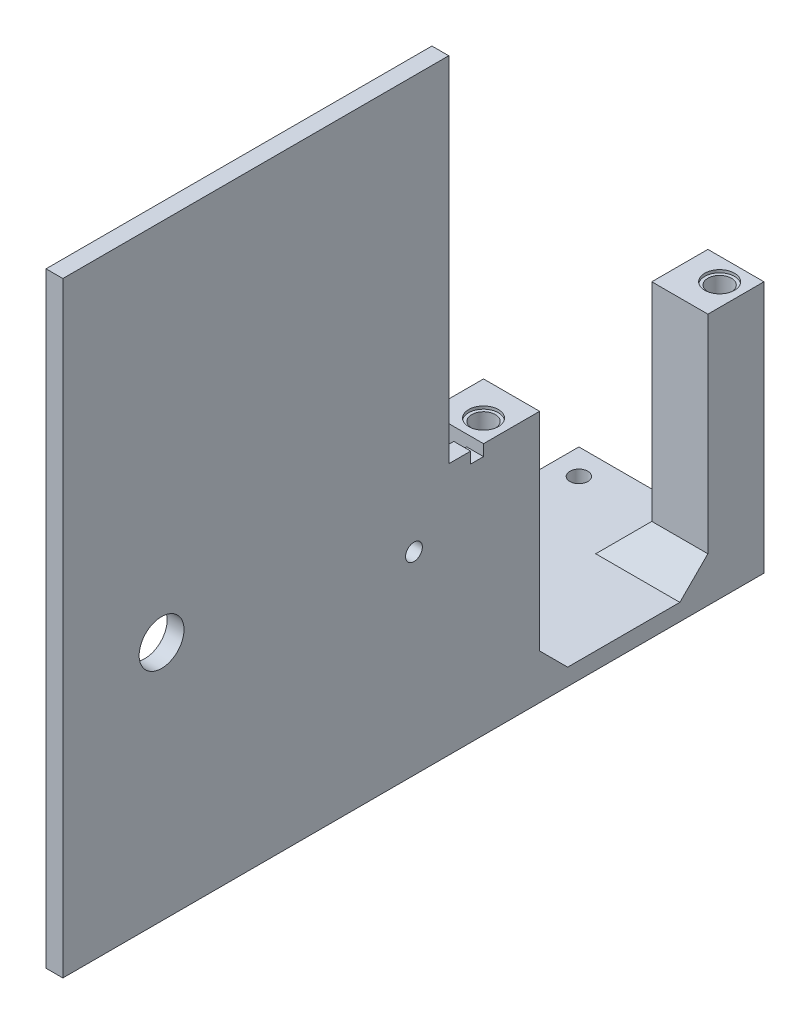
SolidWorks part; units mm, degrees
ref_plane "Front Plane" through (0, 0, 0) normal (0, 0, 1) x (1, 0, 0)
ref_plane "Top Plane" through (0, 0, 0) normal (0, 1, 0) x (1, 0, 0)
ref_plane "Right Plane" through (0, 0, 0) normal (1, 0, 0) x (0, 0, -1)
sketch "Sketch1" plane through (0, 0, 0) normal (0, 1, 0) x (1, 0, 0)
  line L1 (-6.5124, 9.686) -> (1.4876, 9.686)
  line L2 (-6.5124, 9.686) -> (-6.5124, -40.314)
  line L3 (-6.5124, -40.314) -> (1.4876, -40.314)
  line L4 (1.4876, 9.686) -> (1.4876, -40.314)
  line L5 (1.4876, 9.686) -> (26.4876, 9.686)
  line L6 (1.4876, 9.686) -> (1.4876, -40.314)
  line L7 (1.4876, -40.314) -> (26.4876, -40.314)
  line L8 (26.4876, 9.686) -> (26.4876, -40.314)
  circle A0 centre (-1.9624, -35.764) radius 1.6
  circle A1 centre (-1.9624, 5.136) radius 1.6
  dimension "D4" = 3.2
  dimension "D5" = 3.2
  dimension "D6" = 4.55
  dimension "D7" = 4.55
  dimension "D8" = 4.55
  dimension "D9" = 4.55
  dimension "D1" = 8
  dimension "D2" = 50
  dimension "D3" = 25
extrude "Boss-Extrude1" add sketch "Sketch1" along normal blind 3 contours A1 | A0 | L5 L8 L7 L3 L2 L1
sketch "Sketch2" plane through (0, 3, 0) normal (0, 1, 0) x (1, 0, 0)
  line L1 (26.4876, -40.314) -> (16.4876, -40.314)
  line L2 (26.4876, -40.314) -> (26.4876, -30.314)
  line L3 (26.4876, -30.314) -> (16.4876, -30.314)
  line L4 (16.4876, -40.314) -> (16.4876, -30.314)
  line L5 (26.4876, 9.686) -> (16.4876, 9.686)
  line L6 (26.4876, 9.686) -> (26.4876, -0.314)
  line L7 (26.4876, -0.314) -> (16.4876, -0.314)
  line L8 (16.4876, 9.686) -> (16.4876, -0.314)
  dimension "D1" = 10
  dimension "D2" = 10
  dimension "D3" = 10
  dimension "D4" = 10
extrude "Boss-Extrude2" add sketch "Sketch2" along normal blind 42
chamfer "Chamfer1" distance 5 angle 45 4 edges at (16.4876, 3, -4.686) (21.4876, 3, 0.314) (16.4876, 3, 35.314) (21.4876, 3, 30.314)
ref_plane "Plane1" through (0, 45, 0) normal (0, 1, 0) x (1, 0, 0)
sketch "Sketch3" plane through (0, 45, 0) normal (0, 1, 0) x (1, 0, 0)
  line L0 (26.4876, -40.314) -> (26.4876, -30.314) construction
  line L1 (16.4876, -40.314) -> (26.4876, -40.314) construction
  line L2 (26.4876, -0.314) -> (26.4876, 9.686) construction
  line L3 (26.4876, 9.686) -> (16.4876, 9.686) construction
  circle A0 centre (22.5376, -36.364) radius 2.1
  circle A1 centre (22.5376, 5.736) radius 2.1
  dimension "D1" = 4.2
  dimension "D3" = 3.95
  dimension "D4" = 4.2
  dimension "D6" = 3.95
  dimension "D2" = 3.95
  dimension "D5" = 3.95
extrude "Cut-Extrude1" cut sketch "Sketch3" against normal blind 52
sketch "Sketch4" plane through (0, 45, 0) normal (0, 1, 0) x (1, 0, 0)
  circle A0 centre (22.5376, -36.364) radius 2.65
  circle A1 centre (22.5376, 5.736) radius 2.65
  dimension "D1" = 5.3
  dimension "D2" = 5.3
extrude "Cut-Extrude2" cut sketch "Sketch4" against normal blind 0.5
ref_plane "Plane2" through (0, 22.5, 0) normal (0, -1, 0) x (-1, 0, 0)
mirror "Mirror1" about plane through (0, 22.5, 0) normal (0, -1, 0) of "Cut-Extrude2"
sketch "Sketch5" plane through (0, 0, 40.314) normal (0, 0, 1) x (1, 0, 0)
  line L0 (26.4876, 45) -> (26.4876, 0) construction
  line L1 (26.4876, 43) -> (23.4876, 43)
  line L2 (26.4876, 43) -> (26.4876, 0)
  line L3 (26.4876, 0) -> (23.4876, 0)
  line L4 (23.4876, 43) -> (23.4876, 0)
  line L5 (-6.5124, 0) -> (26.4876, 0) construction
  line L6 (16.4876, 45) -> (26.4876, 45) construction
  dimension "D1" = 3
  dimension "D2" = 2
extrude "Boss-Extrude3" add sketch "Sketch5" along normal blind 75
sketch "Sketch6" plane through (0, 43, 0) normal (0, 1, 0) x (1, 0, 0)
  line L0 (23.4876, -115.314) -> (23.4876, -40.314) construction
  line L1 (23.4876, -42.614) -> (26.4876, -42.614)
  line L2 (23.4876, -42.614) -> (23.4876, -46.514)
  line L3 (23.4876, -46.514) -> (26.4876, -46.514)
  line L4 (26.4876, -42.614) -> (26.4876, -46.514)
  line L5 (26.4876, -115.314) -> (26.4876, -40.314) construction
  line L6 (16.4876, -40.314) -> (26.4876, -40.314) construction
  dimension "D1" = 2.3
  dimension "D2" = 3.9
extrude "Boss-Extrude4" add sketch "Sketch6" along normal up to surface (2 mm away) up to face at (22.5376, 45, 39.014)
sketch "Sketch7" plane through (0, 43, 0) normal (0, 1, 0) x (1, 0, 0)
  line L1 (23.4876, -115.314) -> (26.4876, -115.314)
  line L2 (23.4876, -115.314) -> (23.4876, -46.514)
  line L3 (23.4876, -46.514) -> (26.4876, -46.514)
  line L4 (26.4876, -115.314) -> (26.4876, -46.514)
extrude "Boss-Extrude5" add sketch "Sketch7" along normal blind 5
sketch "Sketch8" plane through (23.4876, 0, 0) normal (-1, 0, 0) x (0, 0, 1)
  circle A0 centre (52.714, 34.5) radius 1.5
  dimension "D1" = 3
extrude "Cut-Extrude3" cut sketch "Sketch8" against normal blind 5
sketch "Sketch9" plane through (0, 48, 0) normal (0, 1, 0) x (1, 0, 0)
  line L1 (23.4876, -46.514) -> (26.4876, -46.514)
  line L2 (23.4876, -46.514) -> (23.4876, -115.314)
  line L3 (23.4876, -115.314) -> (26.4876, -115.314)
  line L4 (26.4876, -46.514) -> (26.4876, -115.314)
extrude "Boss-Extrude6" add sketch "Sketch9" along normal blind 15
sketch "Sketch10" plane through (23.4876, 0, 0) normal (-1, 0, 0) x (0, 0, 1)
  line L0 (52.714, 34.5) -> (82.714, 34.5) construction
  line L1 (82.714, 34.5) -> (97.714, 34.5) construction
  line L2 (97.714, 34.5) -> (97.714, 43) construction
  line L3 (97.714, 28) -> (97.714, 0) construction
  line L4 (115.314, 0) -> (40.314, 0) construction
  line L5 (97.714, 43) -> (97.714, 28) construction
  circle A0 centre (97.714, 43) radius 4
  dimension "D1" = 28
  dimension "D5" = 8
  dimension "D2" = 30
  dimension "D3" = 15
  dimension "D4" = 15
extrude "Cut-Extrude4" cut sketch "Sketch10" against normal blind 10
sketch "Sketch11" plane through (0, 63, 0) normal (0, 1, 0) x (1, 0, 0)
  line L1 (26.4876, -46.514) -> (23.4876, -46.514)
  line L2 (26.4876, -46.514) -> (26.4876, -115.314)
  line L3 (26.4876, -115.314) -> (23.4876, -115.314)
  line L4 (23.4876, -46.514) -> (23.4876, -115.314)
extrude "Boss-Extrude7" add sketch "Sketch11" along normal blind 45
